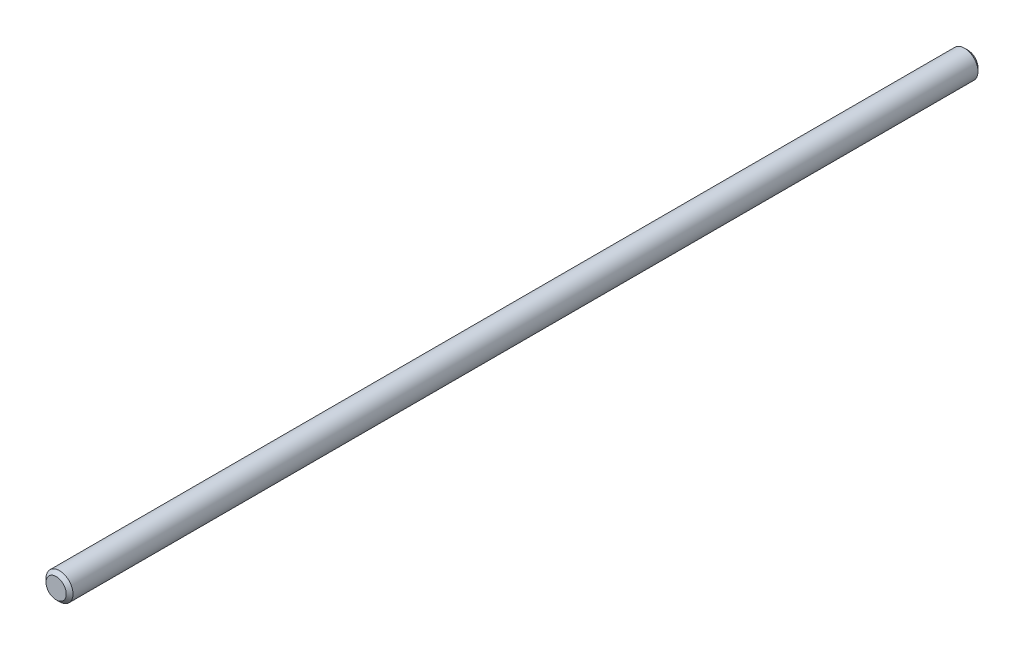
SolidWorks part; units mm, degrees
material "1.0117 (S235J2G4)"
ref_plane "Piano frontale" through (0, 0, 0) normal (0, 0, 1) x (1, 0, 0)
ref_plane "Piano superiore" through (0, 0, 0) normal (0, 1, 0) x (1, 0, 0)
ref_plane "Piano destro" through (0, 0, 0) normal (1, 0, 0) x (0, 0, -1)
sketch "Schizzo1" plane through (0, 0, 0) normal (0, 0, 1) x (1, 0, 0)
  circle A0 centre (0, 0) radius 4
  dimension "D1" = 8
extrude "Estrusione-Estrusione1" add sketch "Schizzo1" along normal blind 270
chamfer "Smusso1" distance 1 angle 45 2 edges at (4, 0, 270) (4, 0, 0)
